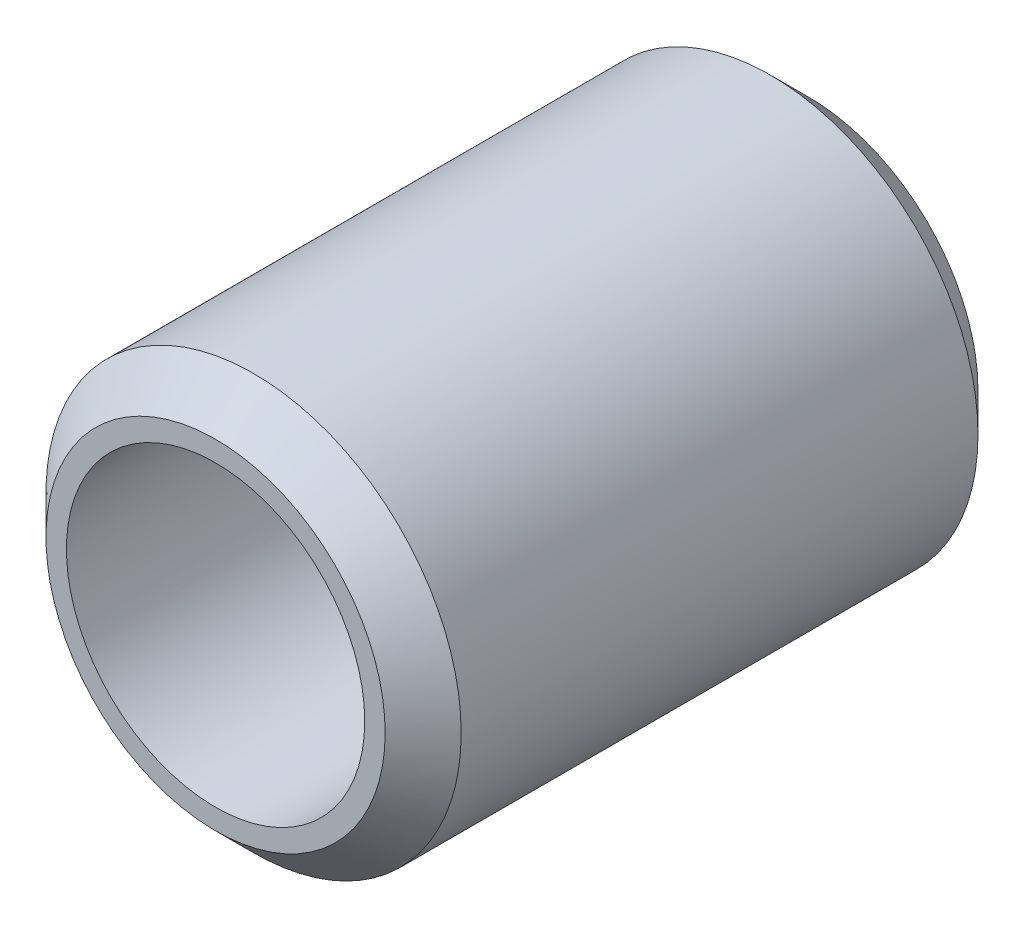
SolidWorks part; units mm, degrees
material "Brass"
ref_plane "Front Plane" through (0, 0, 0) normal (0, 0, 1) x (1, 0, 0)
ref_plane "Top Plane" through (0, 0, 0) normal (0, 1, 0) x (1, 0, 0)
ref_plane "Right Plane" through (0, 0, 0) normal (1, 0, 0) x (0, 0, -1)
sketch "Sketch1" plane through (0, 0, 0) normal (1, 0, 0) x (0, 0, -1)
  line L0 (-3.9624, 2.267) -> (-3.9624, 1.9939)
  line L1 (-3.9624, 1.9939) -> (3.9624, 1.9939)
  line L2 (3.9624, 1.9939) -> (3.9624, 2.267)
  line L3 (3.9624, 2.267) -> (3.4544, 2.775)
  line L4 (3.4544, 2.775) -> (-3.4544, 2.775)
  line L5 (-3.4544, 2.775) -> (-3.9624, 2.267)
  line L6 (3.9624, 0) -> (-3.9624, 0) construction
revolve "Revolve1" add sketch "Sketch1" angle 360 about L6 reverse direction yes
ref_plane "bushing XY" through (0, 0, 0) normal (0, 0, 1) x (1, 0, 0)
ref_plane "bushing XZ" through (0, 0, 0) normal (0, -1, 0) x (-1, 0, 0)
ref_plane "bushing YZ" through (0, 0, 0) normal (1, 0, 0) x (0, 0, -1)
ref_axis "bushing X" through (-80.9, 0, 0) along (1, 0, 0)
ref_axis "bushing Y" through (0, -50, 0) along (0, 1, 0)
ref_axis "bushing Z" through (0, 0, 80.9) along (0, 0, -1)
sketch3d "bushing"
  point P0 (0, 0, 0)
ref_plane "id1 XY" through (0, 0, 0) normal (0, 0, 1) x (1, 0, 0)
ref_plane "id1 XZ" through (0, 0, 0) normal (0, -1, 0) x (-1, 0, 0)
ref_plane "id1 YZ" through (-1.9939, 0, 0) normal (1, 0, 0) x (0, 0, -1)
ref_axis "id1 X" through (-80.9, 0, 0) along (1, 0, 0)
ref_axis "id1 Y" through (-1.9939, -50, 0) along (0, 1, 0)
ref_axis "id1 Z" through (-1.9939, 0, 80.9) along (0, 0, -1)
sketch3d "id1"
  point P0 (-1.9939, 0, 0)
ref_plane "id2 XY" through (0, 0, 0) normal (0, 0, 1) x (1, 0, 0)
ref_plane "id2 XZ" through (0, 0, 0) normal (0, -1, 0) x (-1, 0, 0)
ref_plane "id2 YZ" through (1.9939, 0, 0) normal (1, 0, 0) x (0, 0, -1)
ref_axis "id2 X" through (-80.9, 0, 0) along (1, 0, 0)
ref_axis "id2 Y" through (1.9939, -50, 0) along (0, 1, 0)
ref_axis "id2 Z" through (1.9939, 0, 80.9) along (0, 0, -1)
sketch3d "id2"
  point P0 (1.9939, 0, 0)
ref_plane "id3 XY" through (0, 0, -3.9624) normal (0, 0, -1) x (-1, 0, 0)
ref_plane "id3 XZ" through (0, 0, 0) normal (-1, 0, 0) x (0, 0, 1)
ref_plane "id3 YZ" through (0, 0, 0) normal (0, 1, 0) x (1, 0, 0)
ref_axis "id3 X" through (0, -50, -3.9624) along (0, 1, 0)
ref_axis "id3 Y" through (-80.9, 0, -3.9624) along (1, 0, 0)
ref_axis "id3 Z" through (0, 0, -50) along (0, 0, 1)
sketch3d "id3"
  point P0 (0, 0, -3.9624)
ref_plane "id4 XY" through (0, 0, 3.9624) normal (0, 0, 1) x (1, 0, 0)
ref_plane "id4 XZ" through (0, 0, 0) normal (1, 0, 0) x (0, 0, -1)
ref_plane "id4 YZ" through (0, 0, 0) normal (0, 1, 0) x (1, 0, 0)
ref_axis "id4 X" through (0, -50, 3.9624) along (0, 1, 0)
ref_axis "id4 Y" through (80.9, 0, 3.9624) along (-1, 0, 0)
ref_axis "id4 Z" through (0, 0, 50) along (0, 0, -1)
sketch3d "id4"
  point P0 (0, 0, 3.9624)
